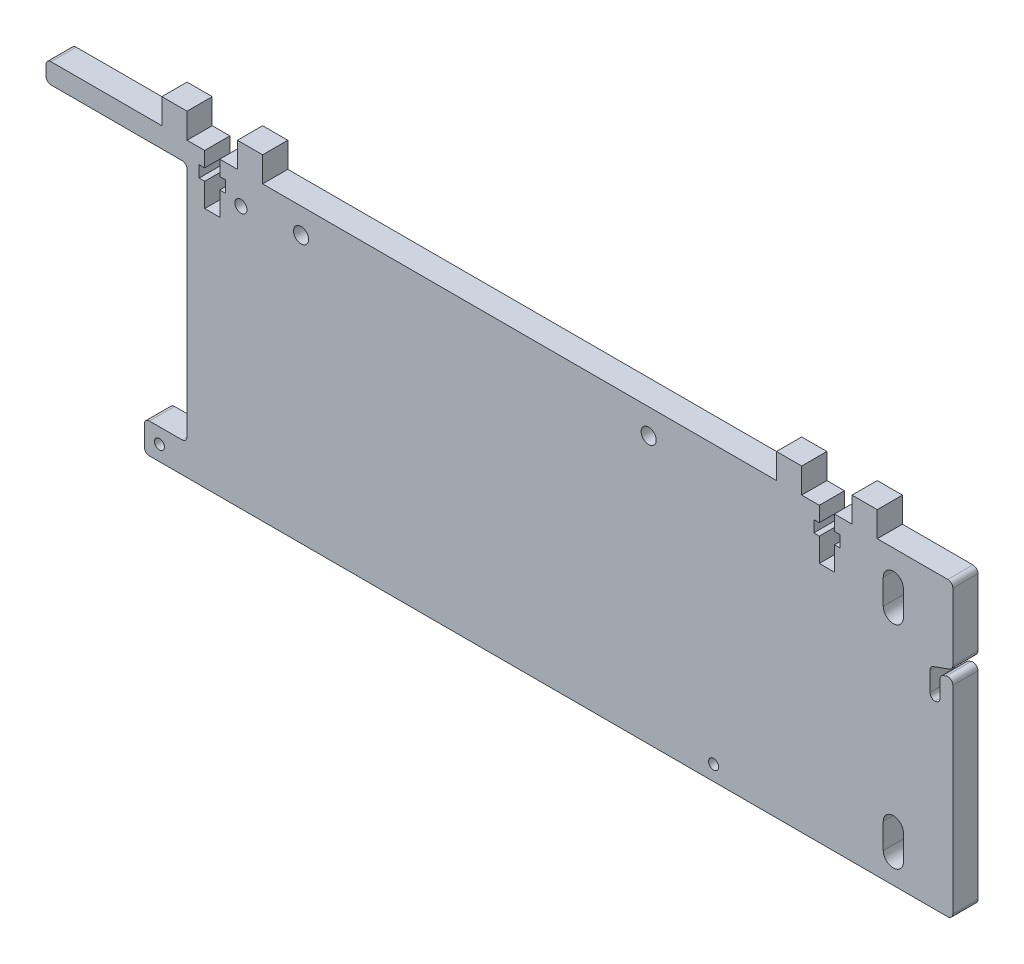
SolidWorks part; units mm, degrees
ref_plane "Plan de face" through (0, 0, 0) normal (0, 0, 1) x (1, 0, 0)
ref_plane "Plan de dessus" through (0, 0, 0) normal (0, 1, 0) x (1, 0, 0)
ref_plane "Plan de droite" through (0, 0, 0) normal (1, 0, 0) x (0, 0, -1)
sketch "Esquisse1" plane through (0, 0, 0) normal (0, 0, 1) x (1, 0, 0)
  line L0 (-90, 0) -> (90, 0) construction
  line L1 (90, 0) -> (90, -58) construction
  line L2 (90, -58) -> (-90, -58) construction
  line L3 (-90, -58) -> (-90, 0) construction
  line L4 (0, 0) -> (0, -58) construction
  line L5 (-67, 0) -> (-90, 0)
  line L6 (-90, 0) -> (-90, -58) construction
  line L7 (90, -58) -> (-62, -58)
  line L8 (90, -58) -> (90, 0)
  line L9 (90, 0) -> (75, 0)
  line L10 (55, 0) -> (-47, 0)
  line L11 (-58.1183, 0) -> (-58.1183, -6) construction
  line L12 (75, 0) -> (75, -6) construction
  line L13 (75, -6) -> (-58.1183, -6) construction
  line L14 (-62, -4) -> (-62, -52)
  line L15 (-51.3092, -6) -> (78.1908, -6) construction
  line L16 (-39.3683, 0) -> (-39.3683, -5) construction
  line L17 (-62, -52) -> (-70.4817, -52)
  line L18 (29.6317, -5) -> (-39.3683, -5) construction
  line L19 (-70.4817, -52) -> (-70.4817, -58)
  line L20 (-62, -58) -> (-62, -4) construction
  line L21 (-62, -4) -> (-90, -4)
  line L22 (-90, -4) -> (-90, 0)
  line L23 (-70.4817, -58) -> (-62, -58)
  circle A2 centre (-39.3683, -5) radius 1.5
  circle A3 centre (29.6317, -5) radius 1.5
  circle A4 centre (-51.3092, -6) radius 1.2
  circle A5 centre (78.1908, -6) radius 1.2
  circle A6 centre (42.5183, -55) radius 1
  circle A8 centre (-67.4817, -55) radius 1
  arc A11 (-66.2317, -55) -> (-68.7317, -55) centre (-67.4817, -55) ccw construction
  arc A13 (41.2683, -55) -> (43.7683, -55) centre (42.5183, -55) ccw construction
  line B0 (67.6, -3) -> (67.6, -5.3)
  line B1 (63.5, -5.3) -> (63.5, -10)
  line B2 (66.5, -10) -> (66.5, -5.3)
  line B3 (67.6, -5.3) -> (66.5, -5.3)
  line B4 (65, 0) -> (65, -11.2208) construction
  line B5 (66.5, 0) -> (70, 0)
  line B6 (70, 5) -> (75, 5)
  line B7 (75, 5) -> (75, 0)
  line B8 (70, 5) -> (70, 0)
  line B9 (63.5, 0) -> (60, 0)
  line B10 (60, 0) -> (60, 5)
  line B11 (60, 5) -> (55, 5)
  line B12 (55, 5) -> (55, 0)
  line B13 (66.5, 0) -> (63.5, 0) construction
  line B14 (63.5, 0) -> (63.5, -3)
  line B15 (63.5, -5.3) -> (62.4, -5.3)
  line B16 (62.4, -3) -> (63.5, -3)
  line B17 (63.5, -10) -> (66.5, -10)
  line B18 (66.5, -3) -> (67.6, -3)
  line B19 (62.4, -5.3) -> (62.4, -3)
  line B20 (66.5, -3) -> (66.5, 0)
  line B21 (65, -10) -> (65, 0) construction
  line B22 (-59.6, -3) -> (-59.6, -5.3)
  line B23 (-55.5, -5.3) -> (-55.5, -10)
  line B24 (-58.5, -10) -> (-58.5, -5.3)
  line B25 (-59.6, -5.3) -> (-58.5, -5.3)
  line B26 (-57, 0) -> (-57, -11.2208) construction
  line B27 (-58.5, 0) -> (-62, 0)
  line B28 (-62, 5) -> (-67, 5)
  line B29 (-67, 5) -> (-67, 0)
  line B30 (-62, 5) -> (-62, 0)
  line B31 (-55.5, 0) -> (-52, 0)
  line B32 (-52, 0) -> (-52, 5)
  line B33 (-52, 5) -> (-47, 5)
  line B34 (-47, 5) -> (-47, 0)
  line B35 (-58.5, 0) -> (-55.5, 0) construction
  line B36 (-55.5, 0) -> (-55.5, -3)
  line B37 (-55.5, -5.3) -> (-54.4, -5.3)
  line B38 (-54.4, -3) -> (-55.5, -3)
  line B39 (-55.5, -10) -> (-58.5, -10)
  line B40 (-58.5, -3) -> (-59.6, -3)
  line B41 (-54.4, -5.3) -> (-54.4, -3)
  line B42 (-58.5, -3) -> (-58.5, 0)
  line B43 (-57, -10) -> (-57, 0) construction
  dimension "D5" = 2.4
  dimension "D8" = 3
  dimension "D11" = 6
  dimension "D16" = 122
  dimension "D17" = 2
  dimension "D2" = 58
  dimension "D3" = 180
  dimension "D4" = 129.5
  dimension "D6" = 18.75
  dimension "D7" = 5
  dimension "D9" = 69
  dimension "D10" = 6
  dimension "D12" = 4
  dimension "D13" = 25
  dimension "D14" = 51.3092
  dimension "D15" = 28
  dimension "D18" = 3
  dimension "D19" = 3
sketch_block_instance "Insert M3 plots ep 5mm-1"
sketch_block "Insert M3 plots ep 5mm" parameters "D1"=10, "D2"=5, "D3"=5
sketch_block_instance "Decoupe Insert M3-4"
sketch_block "Decoupe Insert M3" parameters "D1"=5.2, "D2"=3, "D3"=2.3, "D4"=3, "D5"=10
sketch_block_instance "Insert M3 plots ep 5mm-3"
extrude "Boss.-Extru.1" add sketch "Esquisse1" along normal blind 5 contours B40 B42 B27 B30 B28 B29 L5 L6 L8 L9 B7 B6 B8 B5 B20 B18 B0 B3 B2 B17 B1 B15 B19 B16 B14 B9 B10 B11 B12 L10 B34 B33 B32 B31 B36 B38 B41 B37 B23 B39 B24 B25 B22 region at (12.4382, -28.6909, 0)
sketch "Esquisse2" plane through (0, 0, 0) normal (0, 0, -1) x (-1, 0, 0)
  line L0 (-90, -16.277) -> (-87.46, -17.2015)
  line L1 (-87.46, -17.2015) -> (-87.46, -22.2015)
  line L2 (-87.46, -22.2015) -> (-85.46, -22.2015)
  line L3 (-85.46, -22.2015) -> (-85.46, -16.6524)
  line L4 (-85.46, -16.6524) -> (-90, -15)
  line L5 (-90, -16.277) -> (-90, -15)
  line L6 (-90, -58) -> (-90, 0) construction
  line L7 (-90, 0) -> (-75, 0) construction
  line L8 (-78.1908, -6) -> (-78.1908, -11) construction
  line L9 (-76.1908, -6) -> (-76.1908, -11)
  line L10 (-80.1908, -6) -> (-80.1908, -11)
  line L11 (-78.1908, -48) -> (-78.1908, -53) construction
  line L12 (-76.1908, -48) -> (-76.1908, -53)
  line L13 (-80.1908, -48) -> (-80.1908, -53)
  line L14 (-90, -58) -> (70.4817, -58) construction
  arc A0 (-76.1908, -6) -> (-80.1908, -6) centre (-78.1908, -6) ccw
  arc A1 (-80.1908, -11) -> (-76.1908, -11) centre (-78.1908, -11) ccw
  arc A2 (-76.1908, -48) -> (-80.1908, -48) centre (-78.1908, -48) ccw
  arc A3 (-80.1908, -53) -> (-76.1908, -53) centre (-78.1908, -53) ccw
  point P13 (-78.1908, -8.5)
  point P18 (-78.1908, -50.5)
  dimension "D1" = 1.2
  dimension "D2" = 2
  dimension "D3" = 5
  dimension "D4" = 2.54
  dimension "D5" = 15
  dimension "D6" = 110
  dimension "D7" = 5
  dimension "D8" = 5
  dimension "D9" = 4
  dimension "D10" = 5
extrude "Enlèv. mat.-Extru.1" cut sketch "Esquisse2" against normal through all
fillet "Congé1" radius 1 14 edges at (85.46, -16.6524, 2.5) (90, -15, 2.5) (90, -16.277, 2.5) (87.46, -17.2015, 2.5) (87.46, -22.2015, 2.5) (85.46, -22.2015, 2.5) (90, -58, 2.5) (90, 0, 2.5) (-90, 0, 2.5) (-90, -4, 2.5) (-62, -4, 2.5) (-62, -52, 2.5) (-70.4817, -58, 2.5) (-70.4817, -52, 2.5)
